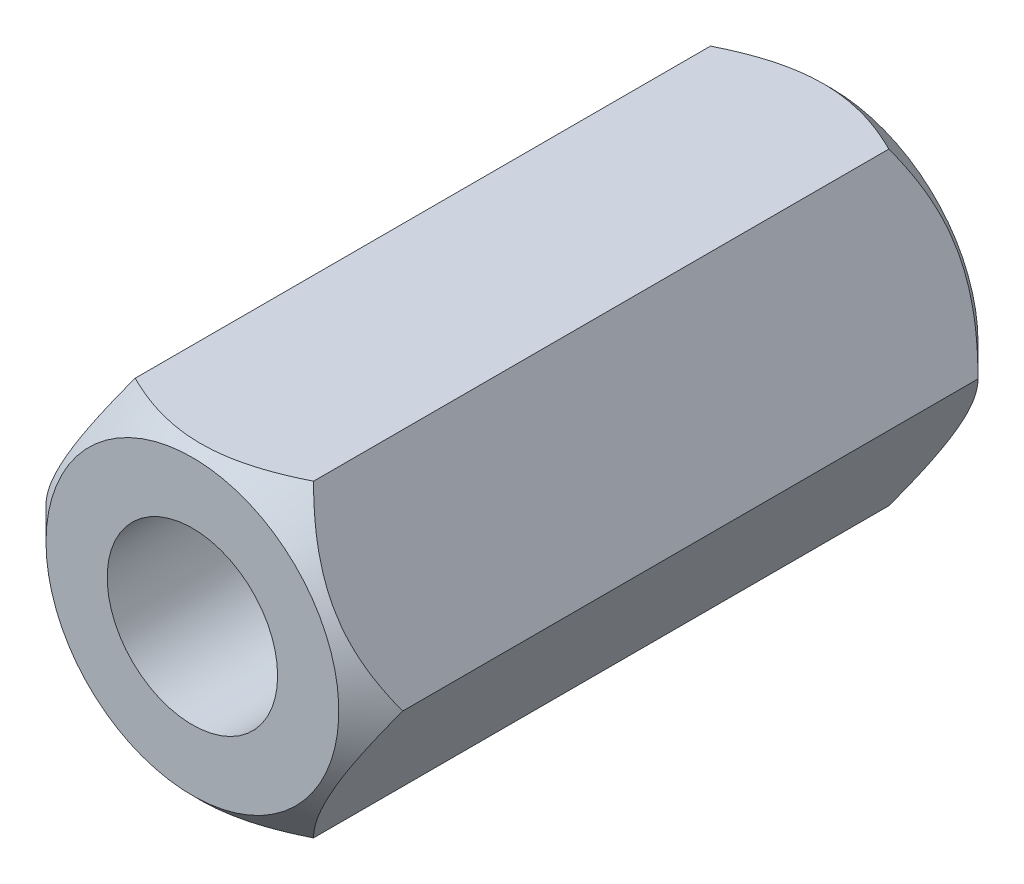
SolidWorks part; units mm, degrees
ref_plane "Спереди" through (0, 0, 0) normal (0, 0, 1) x (1, 0, 0)
ref_plane "Сверху" through (0, 0, 0) normal (0, 1, 0) x (1, 0, 0)
ref_plane "Справа" through (0, 0, 0) normal (1, 0, 0) x (0, 0, -1)
sketch "Эскиз1" plane through (0, 0, 0) normal (0, 0, 1) x (1, 0, 0)
  line L1 (1.6743, 0) -> (0.8372, 1.45)
  line L2 (0.8372, 1.45) -> (-0.8372, 1.45)
  line L3 (-0.8372, 1.45) -> (-1.6743, 0)
  line L4 (-1.6743, 0) -> (-0.8372, -1.45)
  line L5 (-0.8372, -1.45) -> (0.8372, -1.45)
  line L6 (0.8372, -1.45) -> (1.6743, 0)
  circle A0 centre (0, 0) radius 1.45 construction
  point P1 (1.6412, 0.3311)
  dimension "D1" = 2.9
extrude "Бобышка-Вытянуть1" add sketch "Эскиз1" along normal mid plane 6
hole_wizard "Отверстие обработанное метчиком M21" positions "Эскиз2" profile "Эскиз3" tap size "M2" standard "DIN" end condition through all
sketch "Эскиз2" plane through (0, 0, 3) normal (0, 0, 1) x (1, 0, 0)
  point P0 (0, 0)
sketch "Эскиз3" plane through (0, 0, 3) normal (1, 0, 0) x (0, -1, 0)
  line L0 (0, 0) -> (0, 6)
  line L1 (0, 6) -> (0.8, 6)
  line L2 (0.8, 6) -> (0.8, 0)
  line L5 (0.8, 0) -> (0, 0)
  line L11 (0, -6.35) -> (0, 107.95) construction
  dimension "Диаметр проходного сверла" = 1.6
  dimension "Глубина проходного сверла" = 6
cosmetic thread "Отверстие резьбы1" parameters "D2"=2
ref_axis "Ось1" through (0, 0, -3) along (0, 0, 1)
sketch "Эскиз4" plane through (0, 0, 0) normal (0, 1, 0) x (0, 0, -1)
  line L0 (3, 1.3743) -> (2.7, 1.6743)
  line L1 (3, -1.6743) -> (3, -0.8372) construction
  line L3 (2.7, 1.6743) -> (3, 1.6743)
  line L4 (3, 1.6743) -> (3, 1.3743)
  line L5 (0, 1.595) -> (0, -1.595) construction
  line L6 (-3, 1.6743) -> (-3, 1.3743)
  line L7 (-2.7, 1.6743) -> (-3, 1.6743)
  line L8 (-3, 1.3743) -> (-2.7, 1.6743)
  dimension "D1" = 0.3
revolve "Вырез-Повернуть1" cut sketch "Эскиз4" angle 360 about axis through (0, 0, -3) along (0, 0, 1)
